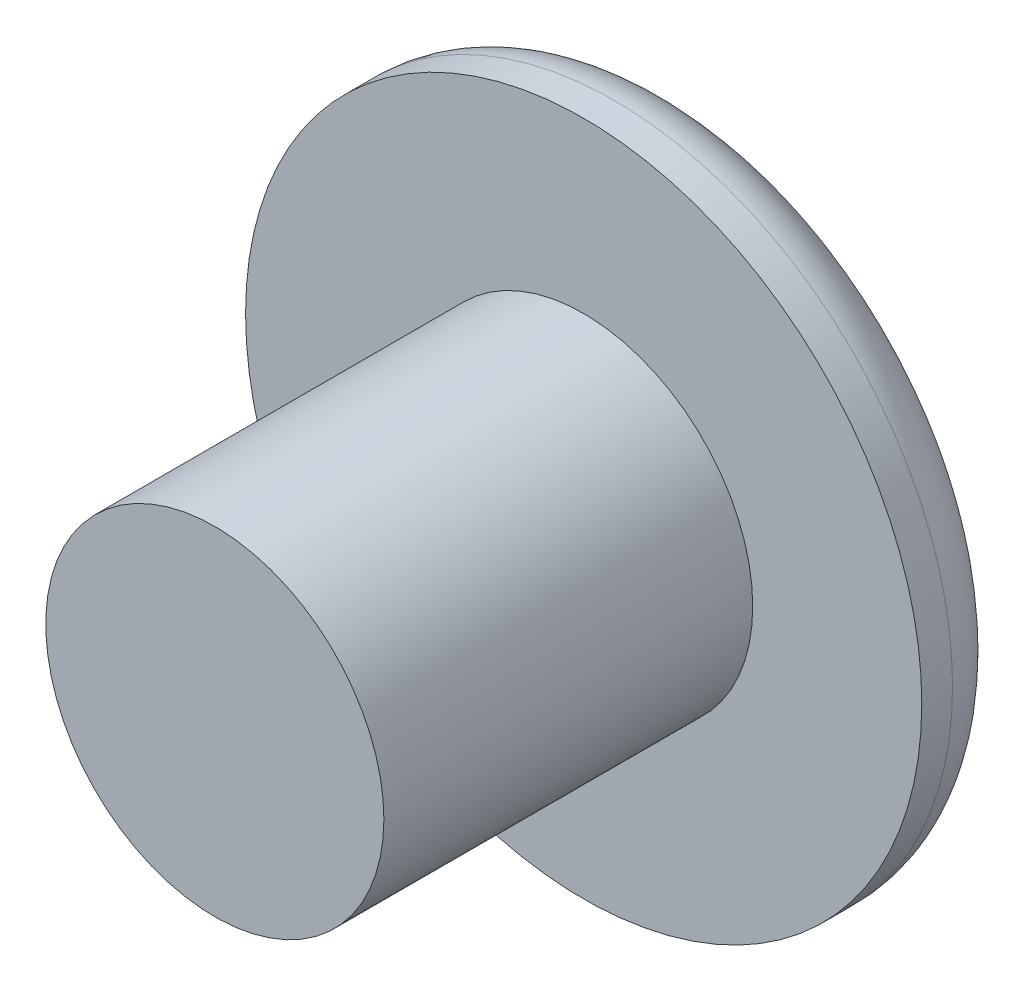
SolidWorks part; units mm, degrees
ref_plane "Front Plane" through (0, 0, 0) normal (0, 0, 1) x (1, 0, 0)
ref_plane "Top Plane" through (0, 0, 0) normal (0, 1, 0) x (1, 0, 0)
ref_plane "Right Plane" through (0, 0, 0) normal (1, 0, 0) x (0, 0, -1)
sketch "Sketch1" plane through (0, 0, 0) normal (0, 0, 1) x (1, 0, 0)
  circle A0 centre (0, 0) radius 5.5
  circle A1 centre (0, 0) radius 11
  dimension "D1" = 11
  dimension "D2" = 22
extrude "Boss-Extrude1" add sketch "Sketch1" along normal blind 12 contours A0 region at (0, 0, 0)
extrude "Boss-Extrude2" add sketch "Sketch1<4>" against normal blind 3 separate body
sketch "Sketch1<4>" plane through (0, 0, 0) normal (0, 0, 1) x (1, 0, 0) same geometry as "Sketch1"
extrude "Boss-Extrude3" add sketch "Sketch1<5>" against normal blind 3 contours A0 region at (0, 0, 0)
sketch "Sketch1<5>" plane through (0, 0, 0) normal (0, 0, 1) x (1, 0, 0) same geometry as "Sketch1"
fillet "Fillet1" radius 2 1 edges at (11, 0, -3)
